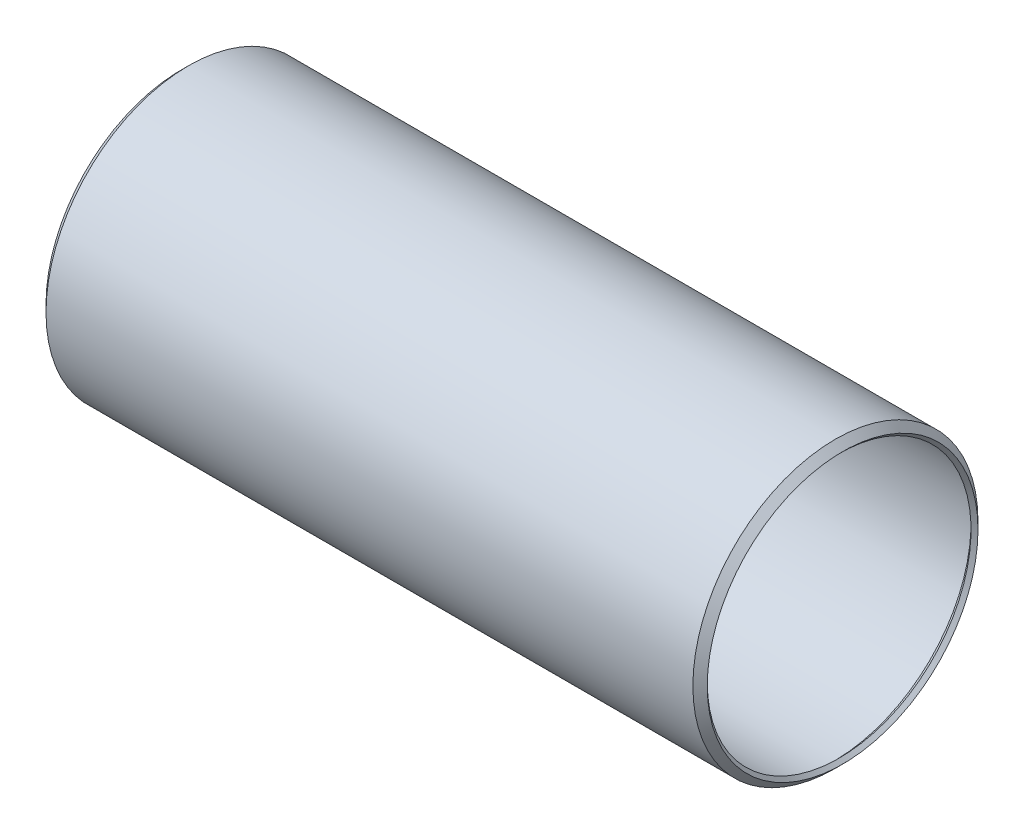
SolidWorks part; units mm, degrees
ref_plane "Front Plane" through (0, 0, 0) normal (0, 0, 1) x (1, 0, 0)
ref_plane "Top Plane" through (0, 0, 0) normal (0, 1, 0) x (1, 0, 0)
ref_plane "Right Plane" through (0, 0, 0) normal (1, 0, 0) x (0, 0, -1)
sketch "Sketch1" plane through (0, 0, 0) normal (0, 0, 1) x (1, 0, 0)
  line L0 (-113.7782, 25.1576) -> (-113.1316, 24.511)
  line L1 (-113.1316, 24.511) -> (-112.0648, 25.5778)
  line L2 (-112.0648, 25.5778) -> (7.3914, 25.5778)
  line L3 (7.3914, 25.5778) -> (8.4582, 24.511)
  line L4 (8.4582, 24.511) -> (9.1048, 25.1576)
  line L5 (9.1048, 25.1576) -> (7.7702, 26.4922)
  line L6 (7.7702, 26.4922) -> (-112.4436, 26.4922)
  line L7 (-112.4436, 26.4922) -> (-113.7782, 25.1576)
  line L8 (7.3914, 0) -> (-112.0648, 0) construction
revolve "Revolve1" add sketch "Sketch1" angle 360 about L8 reverse direction yes
ref_plane "Plane1" through (-64.0207, 0, 0) normal (1, 0, 0) x (0, 0, -1)
ref_plane "Plane2" through (42.8752, 0, 0) normal (1, 0, 0) x (0, 0, -1)
ref_plane "Plane3" through (-178.6128, 0, 0) normal (1, 0, 0) x (0, 0, -1)
ref_plane "Plane4" through (-104.6734, 0, 0) normal (1, 0, 0) x (0, 0, -1)
ref_plane "Plane5" through (0, 0, 0) normal (1, 0, 0) x (0, 0, -1)
ref_plane "Plane6" through (-178.6128, 0, 0) normal (1, 0, 0) x (0, 0, -1)
ref_plane "to_dummy XY" through (-104.6734, 0, 0) normal (-1, 0, 0) x (0, 0, 1)
ref_plane "to_dummy XZ" through (0, 0, 0) normal (0, 1, 0) x (1, 0, 0)
ref_plane "to_dummy YZ" through (0, 0, 0) normal (0, 0, -1) x (-1, 0, 0)
ref_axis "to_dummy X" through (-104.6734, 0, 80.9) along (0, 0, -1)
ref_axis "to_dummy Y" through (-104.6734, 50, 0) along (0, -1, 0)
ref_axis "to_dummy Z" through (-80.9, 0, 0) along (1, 0, 0)
sketch3d "to_dummy"
  point P0 (-104.6734, 0, 0)
ref_plane "to_dummy1 XY" through (-64.0207, 0, 0) normal (-1, 0, 0) x (0, 0, 1)
ref_plane "to_dummy1 XZ" through (0, 0, 0) normal (0, 1, 0) x (1, 0, 0)
ref_plane "to_dummy1 YZ" through (0, 0, 0) normal (0, 0, -1) x (-1, 0, 0)
ref_axis "to_dummy1 X" through (-64.0207, 0, 80.9) along (0, 0, -1)
ref_axis "to_dummy1 Y" through (-64.0207, 50, 0) along (0, -1, 0)
ref_axis "to_dummy1 Z" through (-80.9, 0, 0) along (1, 0, 0)
sketch3d "to_dummy1"
  point P0 (-64.0207, 0, 0)
ref_plane "to_front XY" through (-104.6734, 0, 0) normal (1, 0, 0) x (0, 0, -1)
ref_plane "to_front XZ" through (0, 0, 0) normal (0, -1, 0) x (-1, 0, 0)
ref_plane "to_front YZ" through (0, 0, 0) normal (0, 0, -1) x (-1, 0, 0)
ref_axis "to_front X" through (-104.6734, 0, 80.9) along (0, 0, -1)
ref_axis "to_front Y" through (-104.6734, -50, 0) along (0, 1, 0)
ref_axis "to_front Z" through (80.9, 0, 0) along (-1, 0, 0)
sketch3d "to_front"
  point P0 (-104.6734, 0, 0)
ref_plane "to_rear XY" through (0, 0, 0) normal (-1, 0, 0) x (0, 0, 1)
ref_plane "to_rear XZ" through (0, 0, 0) normal (0, 1, 0) x (1, 0, 0)
ref_plane "to_rear YZ" through (0, 0, 0) normal (0, 0, -1) x (-1, 0, 0)
ref_axis "to_rear X" through (0, 0, 80.9) along (0, 0, -1)
ref_axis "to_rear Y" through (0, 50, 0) along (0, -1, 0)
ref_axis "to_rear Z" through (-80.9, 0, 0) along (1, 0, 0)
sketch3d "to_rear"
  point P0 (0, 0, 0)
